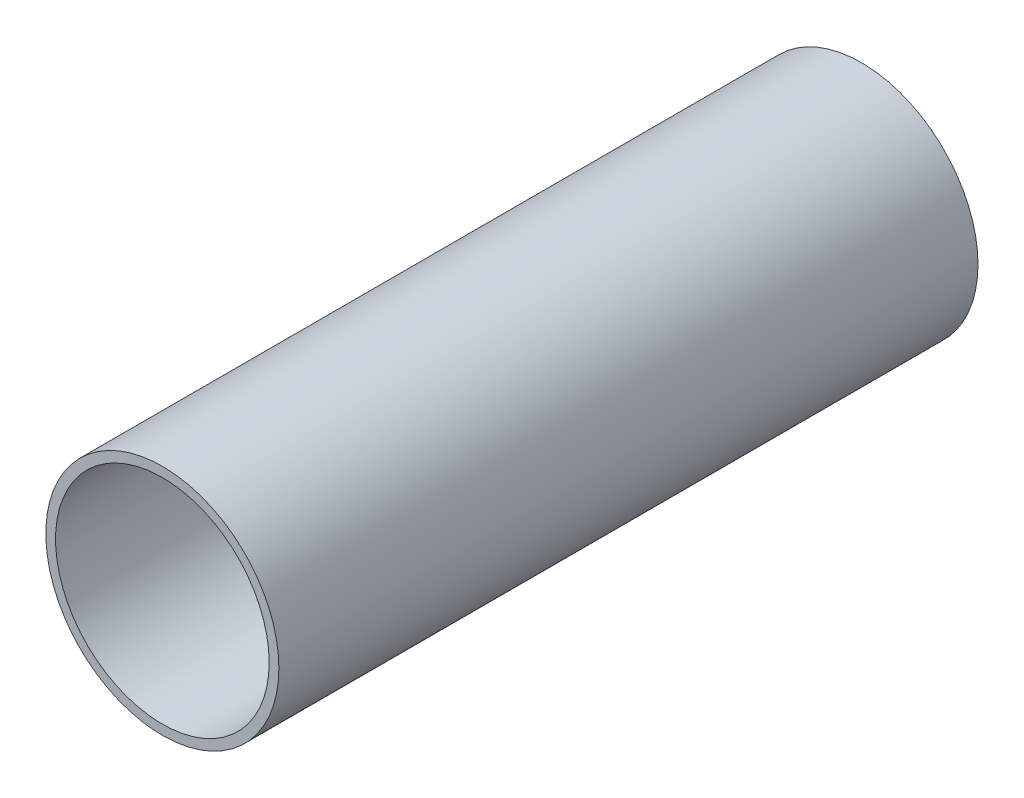
SolidWorks part; units mm, degrees
ref_plane "Front Plane" through (0, 0, 0) normal (0, 0, 1) x (1, 0, 0)
ref_plane "Top Plane" through (0, 0, 0) normal (0, 1, 0) x (1, 0, 0)
ref_plane "Right Plane" through (0, 0, 0) normal (1, 0, 0) x (0, 0, -1)
sketch "Sketch1" plane through (0, 0, 0) normal (0, 0, 1) x (1, 0, 0)
  circle A0 centre (0, 0) radius 63.5
  circle A1 centre (0, 0) radius 69.85
  circle A2 centre (0, 0) radius 76.2
  dimension "D1" = 152.4
  dimension "D2" = 139.7
  dimension "D3" = 127
extrude "Boss-Extrude1" add sketch "Sketch1" along normal blind 444.5 contours A2 A1 region at (-74.0447, 0, 0)
extrude "Boss-Extrude2" add sketch "Sketch1<3>" against normal blind 12.7 contours A1 A0 | A2 A1 region at (-67.8743, 0, 0) region at (-74.0447, 0, 0)
sketch "Sketch1<3>" plane through (0, 0, 0) normal (0, 0, 1) x (1, 0, 0) same geometry as "Sketch1"
